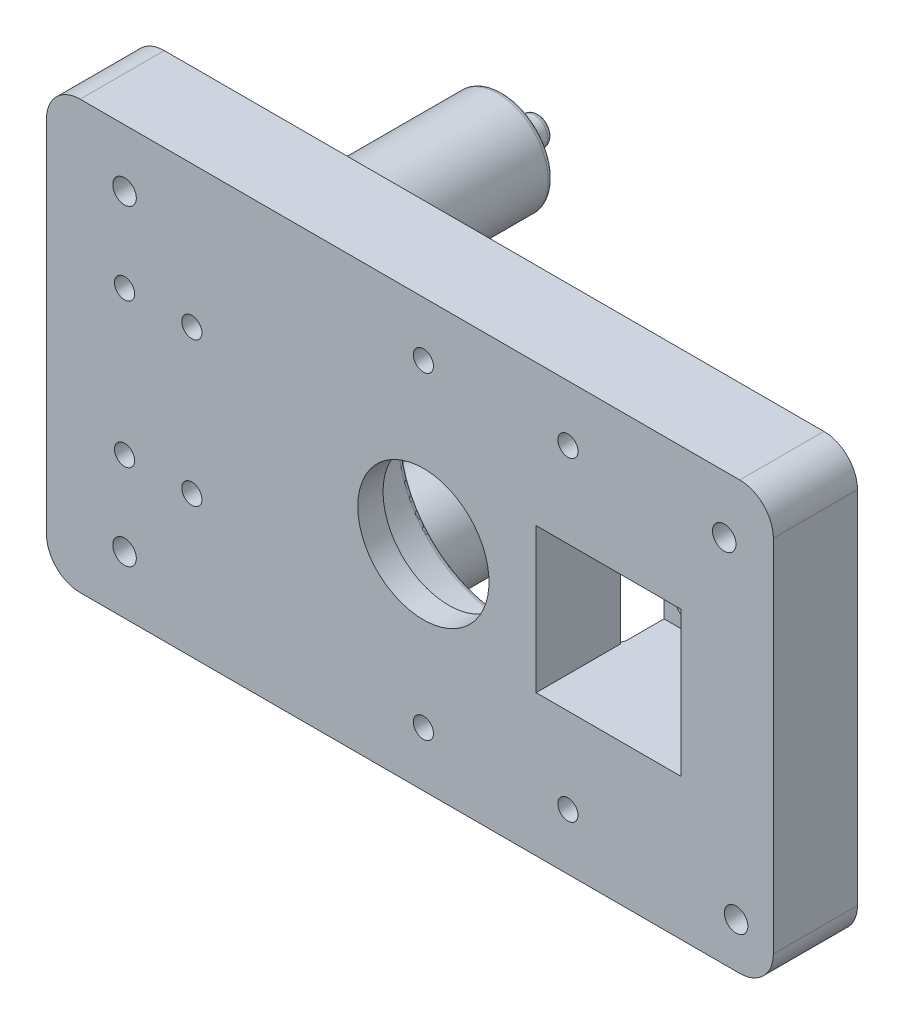
SolidWorks part; units mm, degrees
ref_plane "Front Plane" through (0, 0, 0) normal (0, 0, 1) x (1, 0, 0)
ref_plane "Top Plane" through (0, 0, 0) normal (0, 1, 0) x (1, 0, 0)
ref_plane "Right Plane" through (0, 0, 0) normal (1, 0, 0) x (0, 0, -1)
sketch "Sketch1" plane through (0, 0, 0) normal (0, 0, 1) x (1, 0, 0)
  line L1 (-108, 63.5) -> (108, 63.5)
  line L2 (-108, 63.5) -> (-108, -63.5)
  line L3 (-108, -63.5) -> (108, -63.5)
  line L4 (108, 63.5) -> (108, -63.5)
  line L5 (-108, 63.5) -> (108, -63.5) construction
  line L6 (-108, -63.5) -> (108, 63.5) construction
  point P0 (0, 0)
  dimension "D1" = 127
  dimension "D2" = 216
extrude "Boss-Extrude1" add sketch "Sketch1" along normal blind 25
fillet "Fillet1" radius 10 1 edges at (-108, 63.5, 12.5)
fillet "Fillet2" radius 10 3 edges at (-108, -63.5, 12.5) (108, 63.5, 12.5) (108, -63.5, 12.5)
sketch "Sketch9" plane through (0, 0, 0) normal (0, 0, -1) x (-1, 0, 0)
  line L0 (-98, 63.5) -> (98, 63.5) construction
  line L1 (-37.5, -21.5) -> (-80.5, -21.5)
  line L2 (-37.5, -21.5) -> (-37.5, 21.5)
  line L3 (-37.5, 21.5) -> (-80.5, 21.5)
  line L4 (-80.5, -21.5) -> (-80.5, 21.5)
  line L5 (-37.5, -21.5) -> (-80.5, 21.5) construction
  line L6 (-37.5, 21.5) -> (-80.5, -21.5) construction
  line L8 (108, 0) -> (-108, 0) construction
  line L9 (108, 53.5) -> (108, -53.5) construction
  line L10 (-108, -53.5) -> (-108, 53.5) construction
  circle A0 centre (-4, 0) radius 31
  point P2 (-59, 0)
  dimension "D6" = 62
  dimension "D1" = 27.5
  dimension "D2" = 55
  dimension "D3" = 43
  dimension "D4" = 43
  dimension "D5" = 63.5
extrude "Cut-Extrude4" cut sketch "Sketch9" against normal blind 17.5 contours A0
sketch "Sketch12" plane through (0, 0, 17.5) normal (0, 0, -1) x (-1, 0, 0)
  circle A0 centre (-4, 0) radius 19.5
  dimension "D1" = 39
extrude "Cut-Extrude5" cut sketch "Sketch12" against normal through all
extrude "Cut-Extrude6" cut sketch "Sketch9<4>" against normal through all contours L3 L4 L1 L2
sketch "Sketch9<4>" plane through (0, 0, 0) normal (0, 0, -1) x (-1, 0, 0) same geometry as "Sketch9"
sketch "Sketch13" plane through (0, 0, 0) normal (0, 0, -1) x (-1, 0, 0)
  line L1 (-37.5, -21.5) -> (-80.5, -21.5)
  line L2 (-37.5, -21.5) -> (-37.5, -25.5)
  line L3 (-37.5, -25.5) -> (-80.5, -25.5)
  line L4 (-80.5, -21.5) -> (-80.5, -25.5)
  dimension "D1" = 4
  dimension "D2" = 43
extrude "Boss-Extrude2" add sketch "Sketch13" along normal blind 17
ref_plane "Plane3" through (0, -21.5, 0) normal (0, 1, 0) x (1, 0, 0)
ref_plane "Plane4" through (0, 0, 0) normal (0, 0, -1) x (-1, 0, 0)
ref_plane "Plane6" through (80.5, 0, 0) normal (1, 0, 0) x (0, 0, -1)
sketch "Sketch16" plane through (80.5, 0, 0) normal (1, 0, 0) x (0, 0, -1)
  line L0 (17, -21.5) -> (0, -21.5) construction
  line L1 (17.0075, -21.5) -> (0.1109, -21.5)
  line L2 (17.0075, -21.5) -> (17.0075, -25.5)
  line L3 (17.0075, -25.5) -> (0.1109, -25.5)
  line L4 (0.1109, -21.5) -> (0.1109, -25.5)
  line L5 (17, -25.5) -> (0, -25.5) construction
fillet "Fillet4" radius 2 3 edges at (59, -25.5, 0) (37.5, -23.5, 0) (80.5, -23.5, 0)
sketch "Sketch17" plane through (0, -21.5, 0) normal (0, 1, 0) x (1, 0, 0)
  line L0 (80.5, 17.0075) -> (80.5, 0.1109) construction
  line L1 (37.5, 17) -> (80.5, 17)
  line L2 (37.5, 17) -> (37.5, 13)
  line L3 (37.5, 13) -> (80.5, 13)
  line L4 (80.5, 17) -> (80.5, 13)
  dimension "D1" = 4
extrude "Boss-Extrude5" add sketch "Sketch17" along normal blind 9
sketch "Sketch18" plane through (0, 0, 0) normal (0, 0, -1) x (-1, 0, 0)
  line L1 (-37.5, 21.5) -> (-80.5, 21.5)
  line L2 (-37.5, 21.5) -> (-37.5, 25.5)
  line L3 (-37.5, 25.5) -> (-80.5, 25.5)
  line L4 (-80.5, 21.5) -> (-80.5, 25.5)
  dimension "D1" = 43
  dimension "D2" = 4
extrude "Boss-Extrude6" add sketch "Sketch18" along normal blind 17
ref_plane "Plane7" through (0, 21.5, 0) normal (0, -1, 0) x (-1, 0, 0)
sketch "Sketch19" plane through (0, 21.5, 0) normal (0, -1, 0) x (-1, 0, 0)
  line L0 (-80.5, 17) -> (-80.5, 0) construction
  line L1 (-37.5, 17) -> (-80.5, 17)
  line L2 (-37.5, 17) -> (-37.5, 13)
  line L3 (-37.5, 13) -> (-80.5, 13)
  line L4 (-80.5, 17) -> (-80.5, 13)
  dimension "D1" = 4
extrude "Boss-Extrude7" add sketch "Sketch19" along normal blind 9
fillet "Fillet5" radius 2 3 edges at (37.5, 23.5, 0) (80.5, 23.5, 0) (59, 25.5, 0)
ref_plane "Plane8" through (0, 0, -17) normal (0, 0, -1) x (-1, 0, 0)
sketch "Sketch20" plane through (0, 0, -17) normal (0, 0, -1) x (-1, 0, 0)
  line L0 (-37.5, -25.5) -> (-37.5, -12.5) construction
  line L2 (-80.5, -21.5) -> (-37.5, -21.5)
  line L3 (-80.5, -12.5) -> (-80.5, -25.5) construction
  line L4 (-80.5, -12.5) -> (-37.5, -12.5) construction
  circle A0 centre (-43.15, -16) radius 1.85
  circle A1 centre (-74.85, -16) radius 1.85
  dimension "D3" = 5.5
  dimension "D4" = 3.7
  dimension "D5" = 5.65
  dimension "D6" = 3.7
  dimension "D1" = 5.65
  dimension "D2" = 9
extrude "Cut-Extrude7" cut sketch "Sketch20" against normal blind 9 contours A1 | A0
ref_plane "Plane9" through (0, 0, -17) normal (0, 0, -1) x (-1, 0, 0)
sketch "Sketch23" plane through (0, 0, -17) normal (0, 0, -1) x (-1, 0, 0)
  line L0 (-37.5, 21.5) -> (-80.5, 21.5)
  line L1 (-37.5, 12.5) -> (-37.5, 25.5) construction
  line L2 (-80.5, 25.5) -> (-80.5, 12.5) construction
  line L3 (-37.5, 12.5) -> (-80.5, 12.5) construction
  circle A0 centre (-43.15, 15.85) radius 1.85
  circle A1 centre (-74.85, 16) radius 1.85
  dimension "D4" = 3.7
  dimension "D5" = 3.7
  dimension "D6" = 5.65
  dimension "D7" = 5.65
  dimension "D1" = 9
  dimension "D2" = 5.5
  dimension "D3" = 5.65
extrude "Cut-Extrude8" cut sketch "Sketch23" against normal blind 9 contours A0 | A1
ref_plane "Plane10" through (0, 0, 0) normal (0, 0, -1) x (-1, 0, 0)
sketch "Sketch25" plane through (0, 0, 0) normal (0, 0, -1) x (-1, 0, 0)
  line L0 (5.8491, 5.5555) -> (-31.0008, -15.2301)
  line L1 (-4, -31) -> (-4, 31)
  line L2 (98, -63.5) -> (-98, -63.5) construction
  line L3 (-98, 63.5) -> (98, 63.5) construction
  circle A0 centre (5.8491, 5.5555) radius 0.0422
  circle A1 centre (-4, 0) radius 31 construction
  circle A2 centre (42.4241, -43.5) radius 15
  circle A3 centre (42.4241, 43.5) radius 15
  point P8 (-12.5759, -4.8373)
  dimension "D4" = 20
  dimension "D5" = 30
  dimension "D6" = 30
  dimension "D1" = 55
  dimension "D2" = 55
  dimension "D3" = 20
extrude "Boss-Extrude9" add sketch "Sketch25" along normal blind 45 contours A3 | A2
ref_plane "Plane11" through (0, 0, -45) normal (0, 0, -1) x (-1, 0, 0)
sketch "Sketch26" plane through (0, 0, -45) normal (0, 0, -1) x (-1, 0, 0)
  circle A0 centre (42.4241, -43.5) radius 4.15
  dimension "D1" = 8.3
extrude "Boss-Extrude10" add sketch "Sketch26" along normal blind 10.75
ref_plane "Plane12" through (0, 0, -45) normal (0, 0, -1) x (-1, 0, 0)
sketch "Sketch27" plane through (0, 0, -45) normal (0, 0, -1) x (-1, 0, 0)
  circle A0 centre (42.4241, 43.5) radius 4.15
  dimension "D1" = 8.3
extrude "Boss-Extrude11" add sketch "Sketch27" along normal blind 10.75
fillet "Fillet9" radius 2 1 edges at (-27.4241, -43.5, 0)
fillet "Fillet10" radius 2 1 edges at (-27.4241, 43.5, 0)
ref_plane "Plane13" through (0, 0, 25) normal (0, 0, 1) x (1, 0, 0)
sketch "Sketch28" plane through (0, 0, 25) normal (0, 0, 1) x (1, 0, 0)
  line L0 (98, 63.5) -> (-98, 63.5) construction
  line L3 (-98, -63.5) -> (98, -63.5) construction
  circle A0 centre (-84.8117, 46.37) radius 3.5
  circle A1 centre (-84.8117, -46.37) radius 3.5
  circle A2 centre (96.9146, -50.1726) radius 3.5
  circle A3 centre (93.3991, 46.37) radius 3.5
  dimension "D2" = 7
  dimension "D3" = 17.13
  dimension "D4" = 7
  dimension "D5" = 17.13
  dimension "D6" = 7
  dimension "D7" = 7
  dimension "D1" = 17.13
extrude "Cut-Extrude9" cut sketch "Sketch28" against normal through all
ref_plane "Plane14" through (0, 0, 0) normal (0, 0, -1) x (-1, 0, 0)
sketch "Sketch29" plane through (0, 0, 0) normal (0, 0, -1) x (-1, 0, 0)
  line L0 (-108, 0) -> (108, 0) construction
  line L1 (-108, -53.5) -> (-108, 53.5) construction
  line L2 (108, 53.5) -> (108, -53.5) construction
  line L3 (-4, -31) -> (-4, -63.5) construction
  line L4 (-4, 47.25) -> (-89.8991, 46.37) construction
  line L5 (98, -63.5) -> (-98, -63.5) construction
  line L6 (84.8117, -42.87) -> (84.8117, 0) construction
  line L7 (-4, 31) -> (-4, 63.5) construction
  line L8 (-98, 63.5) -> (98, 63.5) construction
  line L9 (84.8117, 21.435) -> (64.8117, 21.435) construction
  circle A3 centre (-46.9495, 46.81) radius 3
  circle A4 centre (-93.3991, 46.37) radius 3.5 construction
  circle A5 centre (-4, 0) radius 31 construction
  circle A6 centre (-4, 0) radius 31 construction
  circle A7 centre (-4, 47.25) radius 3
  circle A9 centre (-4, -47.25) radius 3
  circle A10 centre (-46.9495, -46.81) radius 3
  circle A11 centre (84.8117, -21.435) radius 3
  circle A12 centre (84.8117, -46.37) radius 3.5 construction
  circle A13 centre (84.8117, 21.435) radius 3
  circle A14 centre (64.8117, 21.435) radius 3
  circle A15 centre (64.8117, -21.435) radius 3
  point P33 (-46.9495, 46.81)
  point P39 (84.8117, -21.435)
  dimension "D1" = 6
  dimension "D2" = 20
extrude "Cut-Extrude11" cut sketch "Sketch29" against normal through all contours A7 | A11 | A9 | A14 | A13 | A15 | A3 | A10
ref_plane "Plane15" through (0, 0, 5) normal (0, 0, -1) x (-1, 0, 0)
ref_plane "Plane16" through (0, 0, 10) normal (0, 0, -1) x (-1, 0, 0)
ref_plane "Plane17" through (0, 0, 17.5) normal (0, 0, -1) x (-1, 0, 0)
fillet "Fillet11" radius 1.5 1 edges at (-27, 0, 0)
fillet "Fillet12" radius 1.5 2 edges at (-57.4241, -43.5, -45) (-57.4241, 43.5, -45)
sketch "Sketch30" plane through (0, 0, -45) normal (0, 0, -1) x (-1, 0, 0)
  line L0 (0, 0) -> (42.7555, 0) construction
  circle A0 centre (42.4241, 43.5) radius 5.6
  circle A1 centre (42.4241, -43.5) radius 5.6
  dimension "D1" = 11.2
fillet "Fillet13" radius 1.5 2 edges at (-46.5741, 43.5, -55.75) (-46.5741, -43.5, -55.75)
extrude "Boss-Extrude13" add sketch "Sketch30" along normal blind 2
